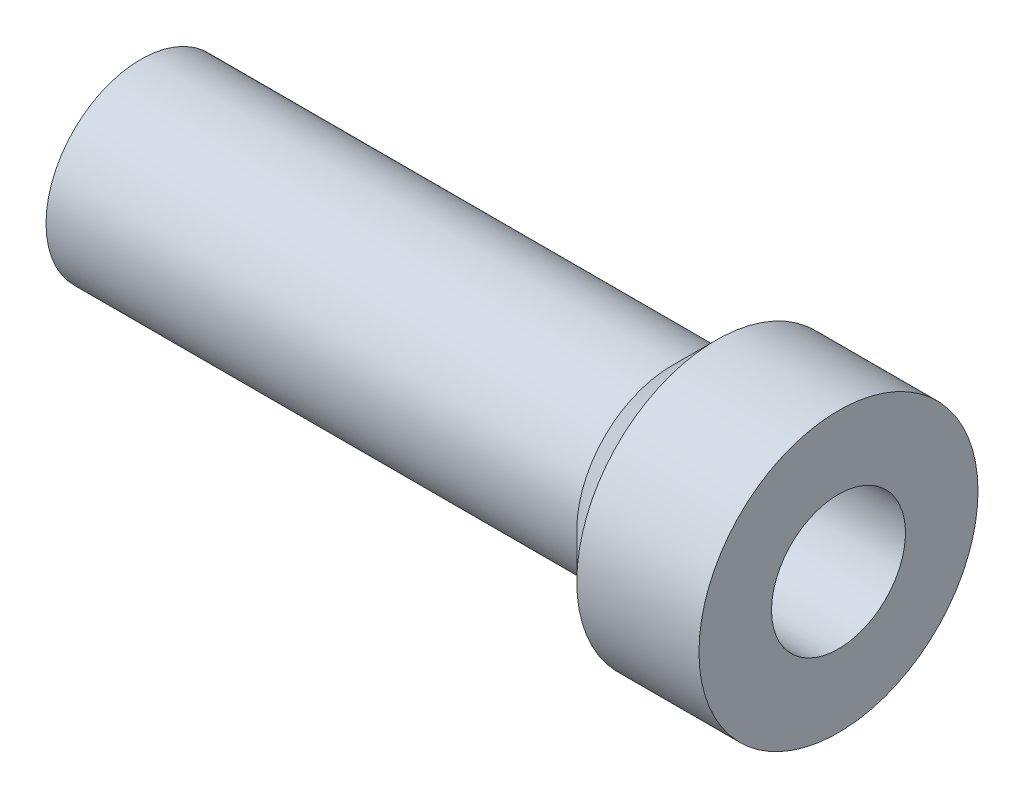
SolidWorks part; units mm, degrees
ref_plane "Front Plane" through (0, 0, 0) normal (0, 0, 1) x (1, 0, 0)
ref_plane "Top Plane" through (0, 0, 0) normal (0, 1, 0) x (1, 0, 0)
ref_plane "Right Plane" through (0, 0, 0) normal (1, 0, 0) x (0, 0, -1)
sketch "Sketch2" plane through (0, 0, 0) normal (0, 0, 1) x (1, 0, 0)
  line L0 (0, 0) -> (64.6823, 0) construction
  line L1 (0, 8.5) -> (0, 6)
  line L2 (0, 6) -> (45, 6)
  line L3 (45, 6) -> (45, 4.25)
  line L4 (45, 4.25) -> (47.5, 4.25)
  line L5 (47.5, 4.25) -> (47.5, 6)
  line L6 (47.5, 6) -> (62.5, 6)
  line L7 (62.5, 6) -> (62.5, 12.5)
  line L8 (62.5, 12.5) -> (51.553, 12.5)
  line L9 (51.553, 12.5) -> (47.553, 8.5)
  line L10 (47.553, 8.5) -> (0, 8.5)
  point P5 (64.6823, 0)
  dimension "D1" = 8.5
  dimension "D2" = 6
  dimension "D3" = 1.75
  dimension "D4" = 2.5
  dimension "D5" = 1.75
  dimension "D6" = 15
  dimension "D7" = 12.5
  dimension "D8" = 45
  dimension "D9" = 14.947
  dimension "D10" = 45
revolve "Revolve1" add sketch "Sketch2" angle 360 about L0
